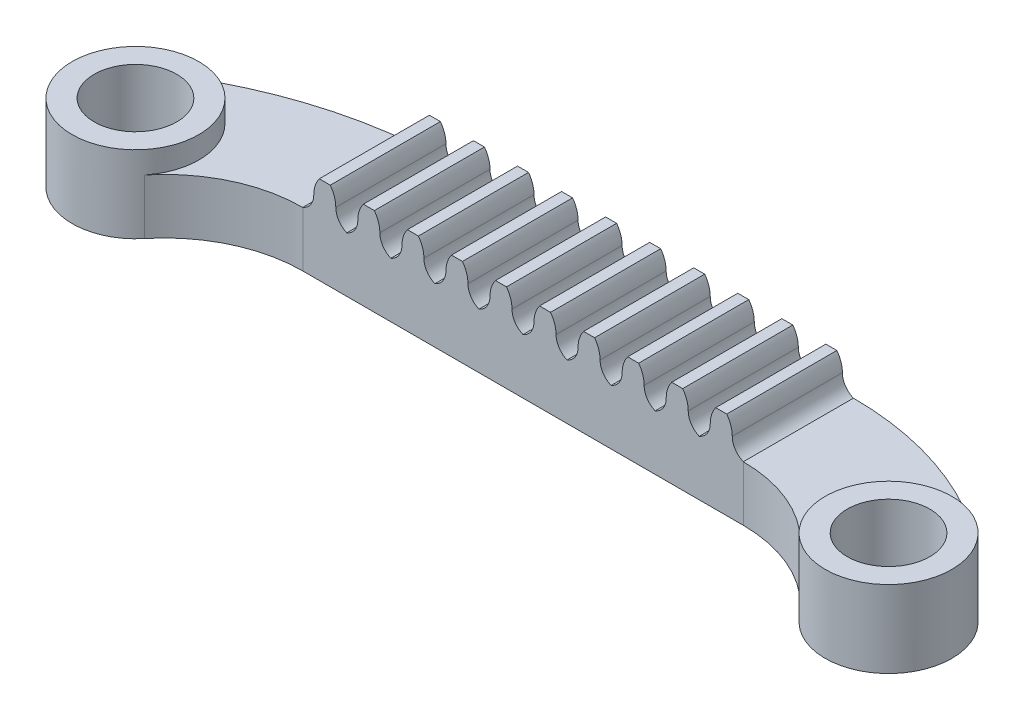
SolidWorks part; units mm, degrees
note: The reader was unsure of these and kept them because the rebuilt part matched: shared geometry of "Sketch1<3>".
ref_plane "Front Plane" through (0, 0, 0) normal (0, 0, 1) x (1, 0, 0)
ref_plane "Top Plane" through (0, 0, 0) normal (0, 1, 0) x (1, 0, 0)
ref_plane "Right Plane" through (0, 0, 0) normal (1, 0, 0) x (0, 0, -1)
sketch "Sketch1" plane through (0, 0, 0) normal (0, 1, 0) x (1, 0, 0)
  line L0 (-34.19, -6) -> (-20, 0)
  line L1 (-20, -5) -> (20, -5)
  line L4 (20, 0) -> (34.19, -6)
  line L5 (-20, 5) -> (20, 5)
  line L6 (-20, -5) -> (-20, 5)
  line L7 (20, -5) -> (20, 5)
  line L8 (-20, 0) -> (20, 0)
  circle A0 centre (-34.19, -6) radius 3.75
  circle A1 centre (34.19, -6) radius 3.75
  circle A2 centre (-34.19, -6) radius 5.75
  circle A3 centre (34.19, -6) radius 5.75
  arc A4 (-29.729, -9.628) -> (-20, -5) centre (-20, -17.5403) cw
  arc A5 (20, -5) -> (29.729, -9.628) centre (20, -17.5403) cw
  arc A6 (37.9325, -1.6346) -> (20, 5) centre (20, -22.5518) ccw
  arc A7 (-20, 5) -> (-37.4199, -1.2429) centre (-16.6042, -31.9009) ccw
  dimension "D1" = 7.5
  dimension "D3" = 2
  dimension "D2" = 68.38
  dimension "D4" = 40
  dimension "D5" = 6
  dimension "D6" = 6
  dimension "D7" = 10
extrude "Boss-Extrude1" add sketch "Sketch1" along normal blind 5
sketch "Sketch2" plane through (0, 0, 0) normal (0, 0, 1) x (1, 0, 0)
  line L0 (-20, 5) -> (-16, 5)
  line L1 (-20, 5) -> (20, 5) construction
  line L2 (-18.5, 8) -> (-17.5, 8)
  line L3 (-19, 6.5) -> (-17, 6.5)
  line L4 (-18, 8) -> (-18, 5)
  line L5 (-17, 6.5) -> (-17, 5)
  line L6 (-20, 5) -> (-30.44, 5)
  line L7 (30.44, 5) -> (20.44, 5)
  arc A0 (-17, 6.5) -> (-17.5, 8) centre (-19.5, 6.5) ccw
  arc A1 (-19, 6.5) -> (-18.5, 8) centre (-16.5, 6.5) cw
  arc A2 (-19, 6.5) -> (-20, 5) centre (-20.625, 6.5) cw
  arc A3 (-16, 5) -> (-17, 6.5) centre (-15.375, 6.5) cw
  point P11 (-18, 6.5)
  dimension "D1" = 4
  dimension "D2" = 3
  dimension "D3" = 1
  dimension "D4" = 2
  dimension "D5" = 10.44
  dimension "D6" = 10
extrude "Boss-Extrude2" add sketch "Sketch2" along normal up to surface and the other way up to surface contours L3 A2 L0 L4 | L5 L3 L4 L0 | L0 A3 L5 | L3 A0 L2 L4 | A1 L3 L4 L2 up to face at (0, 2.5, 5) other way up to face at (0, 2.5, -5)
pattern_linear "LPattern1" count 10 spacing 4 along (1, 0, 0) of "Boss-Extrude2"
extrude "Boss-Extrude3" add sketch "Sketch1<3>" along normal blind 7
sketch "Sketch1<3>" plane through (0, 0, 0) normal (0, 1, 0) x (1, 0, 0) same geometry as "Sketch1"
equation "\"width\"= 68.38"
equation "\"D2@Sketch1\"=\"width\""
